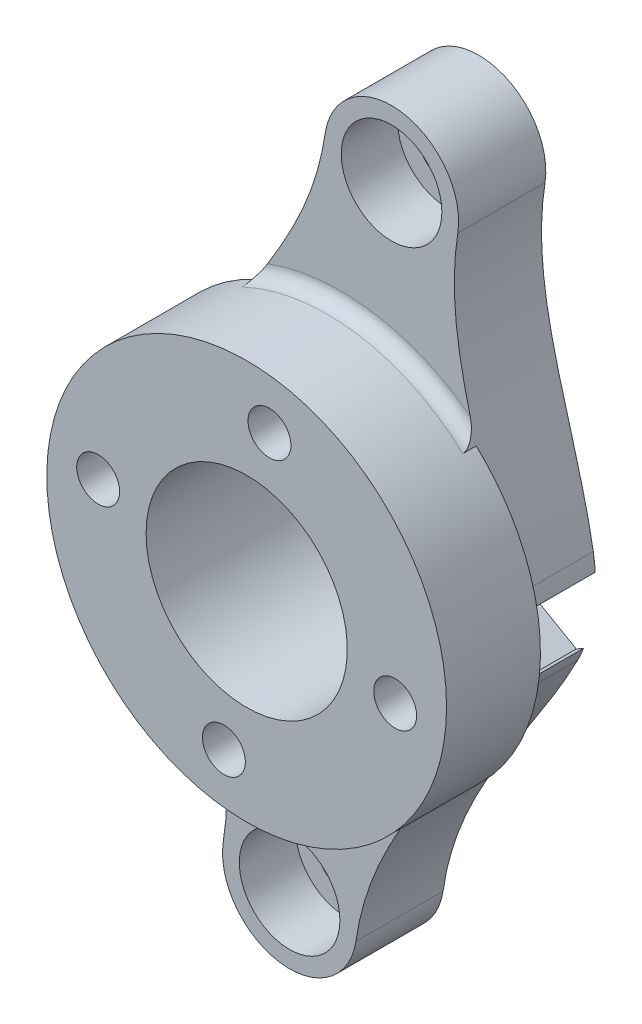
SolidWorks part; units mm, degrees
ref_plane "Front Plane" through (0, 0, 0) normal (0, 0, 1) x (1, 0, 0)
ref_plane "Top Plane" through (0, 0, 0) normal (0, 1, 0) x (1, 0, 0)
ref_plane "Right Plane" through (0, 0, 0) normal (1, 0, 0) x (0, 0, -1)
sketch "Sketch1" plane through (0, 0, 0) normal (0, 0, 1) x (1, 0, 0)
  arc A0 (-11.1727, 5.6055) -> (-12.3393, -1.9981) centre (0, 0) ccw
  circle A4 centre (0, 0) radius 7.5 construction
  circle A8 centre (0, 0) radius 7.5
  arc A11 (8.7426, 24.0121) -> (-1.1417, 25.5287) centre (3.8005, 24.7704) ccw
  circle A12 centre (0, 0) radius 12.5 construction
  arc A13 (1.1532, -25.4498) -> (-8.7299, -23.9334) centre (-3.8005, -24.7704) cw
  arc A14 (11.1727, -5.6055) -> (12.3393, 1.9981) centre (0, 0) ccw
  circle A15 centre (-3.8005, -24.7704) radius 2.25
  circle A16 centre (3.8005, 24.7704) radius 2.25
  spline S0 degree 3 poles (8.7426, 24.0121) (7.4898, 16.3579) (11.0185, 9.6073) (12.3393, 1.9981) knots 0 0 0 0 1 1 1 1
  spline S1 degree 3 poles (-1.1417, 25.5287) (-2.2413, 17.8509) (-7.6314, 12.4687) (-11.1727, 5.6055) knots 0 0 0 0 1 1 1 1
  spline S2 degree 3 poles (1.1417, -25.5287) (2.2413, -17.8509) (7.6314, -12.4687) (11.1727, -5.6055) knots 0 0 0 0 1 1 1 1
  spline S3 degree 3 poles (-8.7426, -24.0121) (-7.4898, -16.3579) (-11.0185, -9.6073) (-12.3393, -1.9981) knots 0 0 0 0 1 1 1 1
  point P10 (3.8005, 24.7704)
  point P25 (0, 0)
  dimension "D1" = 5
extrude "Boss-Extrude1" add sketch "Sketch1" along normal blind 6.5 contours S3 A13 S2 A14 S0 A11 S1 A0 A16 A15 A8
sketch "Sketch2" plane through (0, 0, 6.5) normal (0, 0, 1) x (1, 0, 0)
  circle A0 centre (3.8005, 24.7704) radius 3.75
  circle A1 centre (-3.8005, -24.7704) radius 3.75
extrude "Cut-Extrude1" cut sketch "Sketch2" against normal blind 4.2
sketch "Sketch3" plane through (0, 0, 6.5) normal (0, 0, 1) x (1, 0, 0)
  circle A2 centre (0, 0) radius 7.5 construction
  circle A3 centre (0, 0) radius 7.5
  circle A4 centre (0, 0) radius 14.9
extrude "Boss-Extrude2" add sketch "Sketch3" along normal blind 7
fillet "Fillet1" radius 1 2 edges at (-2.2596, -14.7277, 6.5) (2.2596, 14.7277, 6.5)
sketch "Sketch4" plane through (0, 0, 13.5) normal (0, 0, 1) x (1, 0, 0)
  circle A4 centre (-1.6985, -11.0705) radius 1.6
  circle A5 centre (-11.0705, 1.6985) radius 1.6
  circle A6 centre (1.6985, 11.0705) radius 1.6
  circle A7 centre (11.0705, -1.6985) radius 1.6
  point P19 (0, 0)
  dimension "D1" = 4
extrude "Cut-Extrude2" cut sketch "Sketch4" against normal through all
sketch "Sketch6" plane through (0, 0, 0) normal (0, 0, -1) x (-1, 0, 0)
  line L0 (-11.0705, 1.5346) -> (-13.8705, -0.0819)
  line L1 (-1.5346, -11.0705) -> (0.0819, -13.8705)
  line L2 (0.0819, -13.8705) -> (3.3151, -13.8705)
  line L3 (3.3151, -13.8705) -> (4.9317, -11.0705)
  line L4 (4.9317, -11.0705) -> (3.3151, -8.2705)
  line L5 (3.3151, -8.2705) -> (0.0819, -8.2705)
  line L6 (0.0819, -8.2705) -> (-1.5346, -11.0705)
  line L7 (-13.8705, -0.0819) -> (-13.8705, -3.3151)
  line L8 (-13.8705, -3.3151) -> (-11.0705, -4.9317)
  line L9 (-11.0705, -4.9317) -> (-8.2705, -3.3151)
  line L10 (-8.2705, -3.3151) -> (-8.2705, -0.0819)
  line L11 (-8.2705, -0.0819) -> (-11.0705, 1.5346)
  line L12 (1.5346, 11.0705) -> (-0.0819, 13.8705)
  line L13 (-0.0819, 13.8705) -> (-3.3151, 13.8705)
  line L14 (-3.3151, 13.8705) -> (-4.9317, 11.0705)
  line L15 (-4.9317, 11.0705) -> (-3.3151, 8.2705)
  line L16 (-3.3151, 8.2705) -> (-0.0819, 8.2705)
  line L17 (-0.0819, 8.2705) -> (1.5346, 11.0705)
  line L18 (11.0705, -1.5346) -> (13.8705, 0.0819)
  line L19 (13.8705, 0.0819) -> (13.8705, 3.3151)
  line L20 (13.8705, 3.3151) -> (11.0705, 4.9317)
  line L21 (11.0705, 4.9317) -> (8.2705, 3.3151)
  line L22 (8.2705, 3.3151) -> (8.2705, 0.0819)
  line L23 (8.2705, 0.0819) -> (11.0705, -1.5346)
  circle A0 centre (1.6985, -11.0705) radius 2.8 construction
  point P30 (0, 0)
  dimension "D1" = 4
extrude "Cut-Extrude3" cut sketch "Sketch6" against normal blind 10
